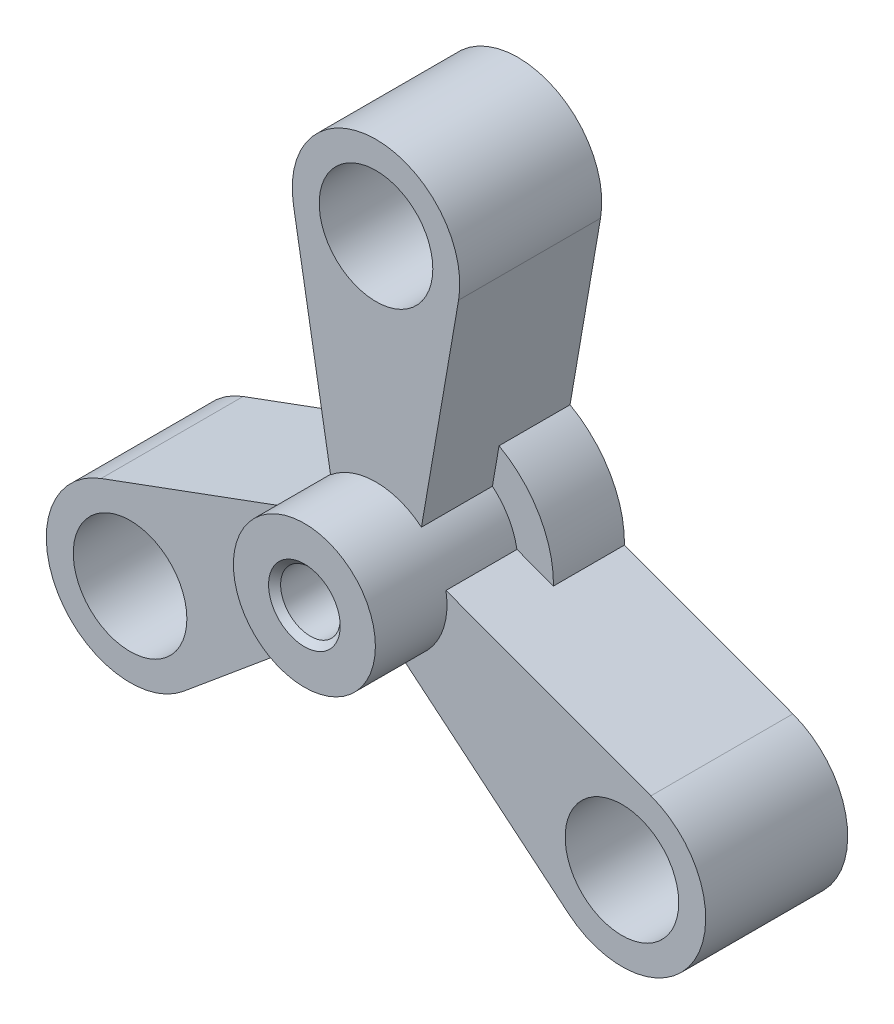
SolidWorks part; units mm, degrees
ref_plane "Front Plane" through (0, 0, 0) normal (0, 0, 1) x (1, 0, 0)
ref_plane "Top Plane" through (0, 0, 0) normal (0, 1, 0) x (1, 0, 0)
ref_plane "Right Plane" through (0, 0, 0) normal (1, 0, 0) x (0, 0, -1)
sketch "Sketch1" plane through (0, 0, 0) normal (0, 0, 1) x (1, 0, 0)
  line L0 (0, 0) -> (0, 20) construction
  line L1 (0, 0) -> (-17.3205, 10) construction
  line L2 (-2.4636, -0.425) -> (-5.8141, 18.997) construction
  line L3 (-5.8141, 18.997) -> (-3.1997, 3.8421)
  line L4 (-6.4952, 3.75) -> (0, 0)
  line L5 (0, 0) -> (0, 25.9)
  arc A0 (-4.3301, 2.5) -> (0, 5) centre (0, 0) cw
  arc A1 (-2.1651, 1.25) -> (0, 2.5) centre (0, 0) cw
  arc A2 (-6.4952, 3.75) -> (0, 7.5) centre (0, 0) cw
  arc A3 (0, 16) -> (0, 24) centre (0, 20) cw
  arc A4 (0, 14.1) -> (0, 25.9) centre (0, 20) cw
  circle A5 centre (0, 0) radius 2.5 construction
  dimension "D2" = 5
  dimension "D3" = 2.5
  dimension "D4" = 7.5
  dimension "D5" = 4
  dimension "D6" = 5.9
  dimension "D1" = 60
  dimension "D7" = 20
extrude "Boss-Extrude1" add sketch "Sketch1" along normal blind 5 contours L4 A1 L5 A0 | A2 L3 A0 L5 | A2 L4 A0 L3 | L5 A4 L3 A2 | A4 L5 A3 | A1 L4 L5 region at (-2.4947, 11.4079, 0) region at (-4.4117, 23.7158, 0) region at (-1.7712, 5.9207, 0) region at (-4.5969, 4.3799, 0) region at (-1.8568, 3.2161, 0) region at (-0.7958, 1.3783, 0)
sketch "Sketch2" plane through (0, 0, 5) normal (0, 0, 1) x (1, 0, 0)
  line L0 (-5.8141, 18.997) -> (-3.1997, 3.8421) construction
  line L1 (-5.8141, 18.997) -> (-3.1997, 3.8421)
  line L2 (-4.3301, 2.5) -> (-2.1651, 1.25)
  line L3 (0, 2.5) -> (0, 25.9)
  line L4 (-2.1651, 1.25) -> (0, 0)
  line L5 (0, 0) -> (0, 2.5)
  arc A0 (0, 25.9) -> (0, 14.1) centre (0, 20) ccw construction
  arc A1 (0, 5) -> (-4.3301, 2.5) centre (0, 0) ccw construction
  arc A2 (0, 25.9) -> (0, 14.1) centre (0, 20) ccw
  arc A3 (0, 5) -> (-4.3301, 2.5) centre (0, 0) ccw
  arc A4 (0, 24) -> (0, 16) centre (0, 20) ccw construction
  arc A5 (0, 24) -> (0, 16) centre (0, 20) ccw
  arc A6 (0, 2.5) -> (-2.1651, 1.25) centre (0, 0) ccw construction
  arc A7 (0, 2.5) -> (-2.1651, 1.25) centre (0, 0) ccw
  line M1 (-6.4952, 3.75) -> (0, 0)
  line M3 (0, 0) -> (0, 16)
  arc M4 (0, 16) -> (0, 24) centre (0, 20) cw
  line M5 (0, 24) -> (0, 25.9)
  arc M6 (0, 25.9) -> (-5.8141, 18.997) centre (0, 20) ccw
  line M7 (-5.8141, 18.997) -> (-3.6657, 6.5431)
extrude "Boss-Extrude3" add sketch "Sketch2" along normal blind 5 contours A3 M3 M1 | A3 L3 A2 L1 M7 | A2 L3 M6 M4 M5 | L4 L5 region at (-2.346, 10.2802, 5) region at (-4.4117, 23.7158, 5) region at (-1.8568, 3.2161, 5) region at (-0.7958, 1.3783, 5)
sketch "Sketch4" plane through (0, 0, 10) normal (0, 0, 1) x (1, 0, 0)
  line L0 (-2.1651, 1.25) -> (-4.3301, 2.5)
  line L1 (0, 2.5) -> (0, 5)
  line L2 (-2.1651, 1.25) -> (0, 0)
  line L3 (0, 0) -> (0, 2.5)
  arc A0 (0, 2.5) -> (-2.1651, 1.25) centre (0, 0) ccw construction
  arc A1 (0, 5) -> (-4.3301, 2.5) centre (0, 0) ccw construction
  arc A2 (0, 2.5) -> (-2.1651, 1.25) centre (0, 0) ccw
  arc A3 (0, 5) -> (-4.3301, 2.5) centre (0, 0) ccw
  line M1 (0, 0) -> (0, 16)
  arc M6 (-3.1997, 3.8421) -> (-4.3301, 2.5) centre (0, 0) ccw
  line M7 (-4.3301, 2.5) -> (0, 0)
extrude "Boss-Extrude4" add sketch "Sketch4" along normal blind 5.0436 contours A2 M1 M7 | A3 A2 M1 M6 M7 region at (-0.7958, 1.3783, 10) region at (-1.8568, 3.2161, 10)
mirror "Mirror1" about plane through (0, 0, 0) normal (1, 0, 0) of bodies 108
ref_axis "Axis1" through (0, 0, 20.9905) along (0, 0, -1)
pattern_circular "CirPattern1" count 3 over 360 about axis through (0, 0, 20.9905) along (0, 0, -1) of bodies 109
combine bodies "Combine1" operation type add bodies to combine 109 120 121
hole_wizard "M5 Tapped Hole1" positions "Sketch7" profile "Sketch8" tap size "M5" standard "ISO" end condition through all
sketch "Sketch7" plane through (0, 0, 15.0436) normal (0, 0, 1) x (1, 0, 0)
  point P0 (0, 0)
sketch "Sketch8" plane through (0, 0, 15.0436) normal (1, 0, 0) x (0, -1, 0)
  line L0 (0, 0) -> (0, 15.0436)
  line L1 (0, 15.0436) -> (2.525, 15.0436)
  line L2 (2.1, 14.6186) -> (2.1, 0.425)
  line L3 (2.1, 0.425) -> (2.525, 0)
  line L5 (2.525, 0) -> (0, 0)
  line L6 (-2.1, 0.425) -> (-2.525, 0) construction
  line L7 (2.525, 15.0436) -> (2.1, 14.6186)
  line L8 (-2.525, 15.0436) -> (-2.1, 14.6186) construction
  line L11 (0, -6.35) -> (0, 107.95) construction
  dimension "Thru Tap Drill Dia." = 4.2
  dimension "Thru Tap Drill Depth" = 15.0436
  dimension "Near C'Sink Dia." = 5.05
  dimension "Near C'Sink Angle" = 90
  dimension "Far C'Sink Dia." = 5.05
  dimension "Far C'Sink Angle" = 90
cosmetic thread "Hole Thread2" parameters "D2"=5
equation "\"D3@Sketch1\"=2.5"
